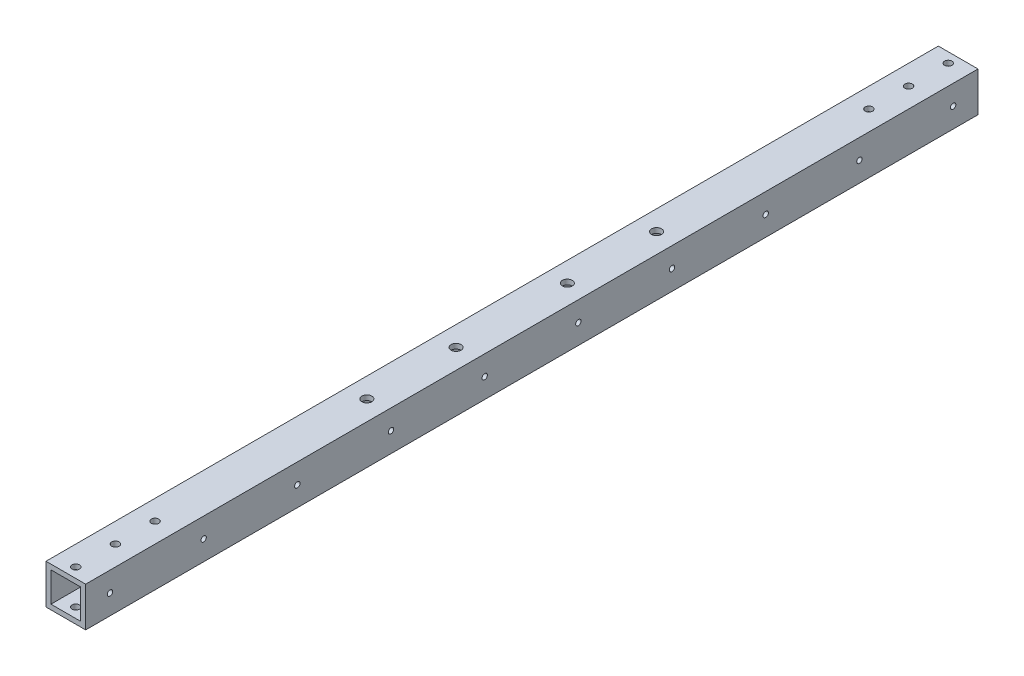
SolidWorks part; units mm, degrees
material "6061-T6 (SS)"
ref_plane "Front Plane" through (0, 0, 0) normal (0, 0, 1) x (1, 0, 0)
ref_plane "Top Plane" through (0, 0, 0) normal (0, 1, 0) x (1, 0, 0)
ref_plane "Right Plane" through (0, 0, 0) normal (1, 0, 0) x (0, 0, -1)
sketch "Sketch1" plane through (0, 0, 0) normal (0, 0, 1) x (1, 0, 0)
  line L1 (-12.7, -12.7) -> (12.7, -12.7)
  line L2 (-12.7, -12.7) -> (-12.7, 12.7)
  line L3 (-12.7, 12.7) -> (12.7, 12.7)
  line L4 (12.7, -12.7) -> (12.7, 12.7)
  line L5 (-12.7, -12.7) -> (12.7, 12.7) construction
  line L6 (-12.7, 12.7) -> (12.7, -12.7) construction
  point P0 (0, 0)
  dimension "D1" = 25.4
  dimension "D2" = 25.4
extrude "Extrude-Thin1" add sketch "Sketch1" along normal blind 571.5 thin thin type one direction reverse wall 3.175
hole_wizard "3/16 (0.1875) Diameter Hole1" positions "3DSketch1" profile "Sketch3" hole size "3/16" standard "ANSI Inch" end condition through all
sketch3d "3DSketch1"
  line L1 (12.7, 12.7, 0) -> (-12.7, 12.7, 0) construction
  line L6 (0, 12.7, 571.5) -> (0, 12.7, 0) construction
  line L7 (12.7, 12.7, 571.5) -> (-12.7, 12.7, 571.5) construction
  point P57 (0, 12.7, 6.35)
  point P59 (0, 12.7, 31.75)
  point P61 (0, 12.7, 57.15)
  point P63 (0, 12.7, 539.75)
  point P65 (0, 12.7, 514.35)
  point P67 (0, 12.7, 565.15)
  dimension "D1" = 25.4
  dimension "D2" = 25.4
  dimension "D3" = 6.35
  dimension "D4" = 25.4
  dimension "D5" = 25.4
  dimension "D6" = 6.35
sketch "Sketch3" plane through (0, 12.7, 565.15) normal (1, 0, 0) x (0, 0, 1)
  line L0 (0, 0) -> (0, 25.4)
  line L1 (0, 25.4) -> (2.3812, 25.4)
  line L2 (2.3812, 25.4) -> (2.3812, 0)
  line L5 (2.3812, 0) -> (0, 0)
  line L11 (0, -6.35) -> (0, 107.95) construction
  dimension "Thru Hole Dia." = 4.7625
  dimension "Thru Hole Depth" = 25.4
hole_wizard "1/4 (0.25) Diameter Hole1" positions "Sketch6" profile "Sketch7" hole size "1/4" standard "ANSI Inch" end condition through all
sketch "Sketch6" plane through (0, 12.7, 0) normal (0, 1, 0) x (1, 0, 0)
  point P0 (0, -321.564)
  point P3 (0, -378.714)
  point P6 (0, -193.167)
  point P9 (0, -250.317)
sketch "Sketch7" plane through (0, 12.7, 321.564) normal (1, 0, 0) x (0, 0, 1)
  line L0 (0, 0) -> (0, 25.4)
  line L1 (0, 25.4) -> (3.175, 25.4)
  line L2 (3.175, 25.4) -> (3.175, 0)
  line L5 (3.175, 0) -> (0, 0)
  line L11 (0, -6.35) -> (0, 107.95) construction
  dimension "Thru Hole Dia." = 6.35
  dimension "Thru Hole Depth" = 25.4
hole_wizard "#8-32 Tapped Hole1" positions "Sketch8" profile "Sketch9" tap size "#8-32" standard "ANSI Inch"
sketch "Sketch8" plane through (12.7, -82.55, 285.75) normal (1, 0, 0) x (0, 0, -1)
  point P0 (-270.1905, 82.55)
  point P3 (-210.1905, 82.55)
  point P6 (-150.1905, 82.55)
  point P9 (-90.1905, 82.55)
  point P12 (-30.1905, 82.55)
  point P15 (29.8095, 82.55)
  point P18 (89.8095, 82.55)
  point P21 (149.8095, 82.55)
  point P24 (209.8095, 82.55)
  point P27 (269.8095, 82.55)
sketch "Sketch9" plane through (12.7, 0, 555.9405) normal (0, 1, 0) x (0, 0, -1)
  line L0 (0, 0) -> (0, 13.3314)
  line L1 (0, 13.3314) -> (1.7272, 12.2936)
  line L2 (1.7272, 12.2936) -> (1.7272, 0)
  line L3 (1.7272, 0) -> (0, 0)
  line L4 (0, 13.3314) -> (-1.7272, 12.2936) construction
  line L5 (0, -6.35) -> (0, 107.95) construction
  dimension "Tap Drill Dia." = 3.4544
  dimension "Tap Drill Depth" = 12.2936
  dimension "Drill Angle" = 118
